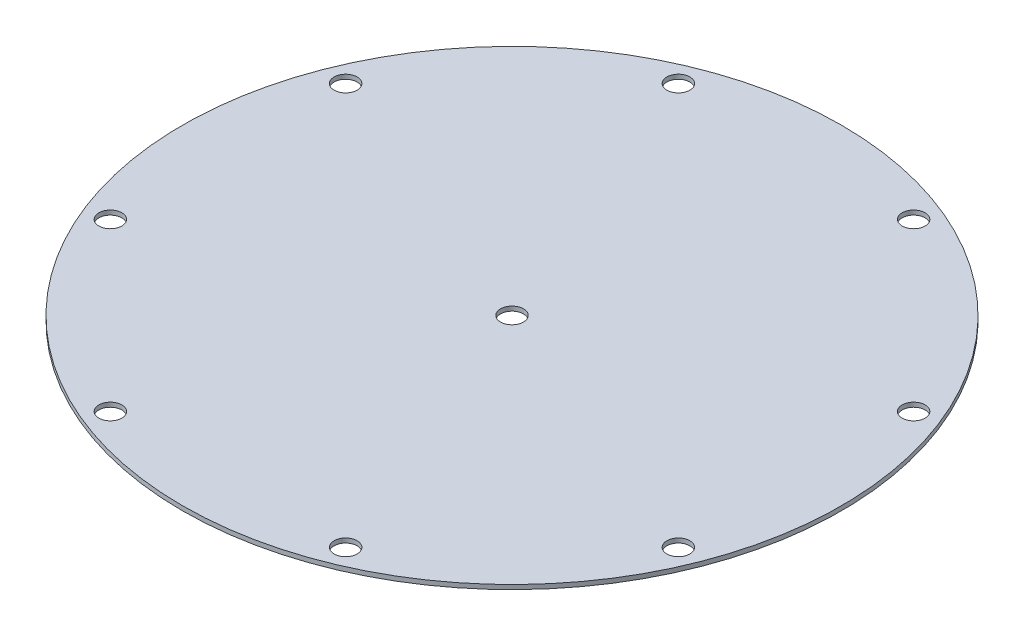
SolidWorks part; units mm, degrees
material "6061-T6 (SS)"
ref_plane "Front Plane" through (0, 0, 0) normal (0, 0, 1) x (1, 0, 0)
ref_plane "Top Plane" through (0, 0, 0) normal (0, 1, 0) x (1, 0, 0)
ref_plane "Right Plane" through (0, 0, 0) normal (1, 0, 0) x (0, 0, -1)
sketch "Sketch2" plane through (0, 0, 0) normal (1, 0, 0) x (0, 0, -1)
  line L0 (0, 0) -> (-74.375, 0)
  line L1 (-74.375, 0) -> (-74.375, 1)
  line L2 (-74.375, 1) -> (0, 1)
  line L5 (0, 1) -> (0, 0)
  dimension "D1" = 74.375
  dimension "D2" = 1
ref_axis "Axis1" through (0, -0.05, 0) along (0, 1, 0)
revolve "Revolve1" add sketch "Sketch2" angle 360 about axis through (0, -0.05, 0) along (0, 1, 0)
hole_wizard "#6 (0.204) Diameter Hole1" positions "Sketch6" profile "Sketch7" hole size "#6" standard "ANSI Inch" end condition through all
sketch "Sketch6" plane through (0, 1, 0) normal (0, 1, 0) x (1, 0, 0)
  line L0 (0, 0) -> (-53.438, 129.0108) construction
  line L2 (0, 0) -> (0, 109.0908) construction
  point P0 (-26.5487, 64.0941)
  dimension "D1" = 22.5
  dimension "D2" = 69.375
sketch "Sketch7" plane through (-26.5487, 1, -64.0941) normal (1, 0, 0) x (0, 0, 1)
  line L0 (0, 0) -> (0, 1)
  line L1 (0, 1) -> (2.5908, 1)
  line L2 (2.5908, 1) -> (2.5908, 0)
  line L5 (2.5908, 0) -> (0, 0)
  line L11 (0, -6.35) -> (0, 107.95) construction
  dimension "Thru Hole Dia." = 5.1816
  dimension "Thru Hole Depth" = 1
pattern_circular "CirPattern3" count 8 over 360 about axis through (0, -0.05, 0) along (0, 1, 0) of "#6 (0.204) Diameter Hole1"
hole_wizard "#6 (0.204) Diameter Hole2" positions "Sketch8" profile "Sketch9" hole size "#6" standard "ANSI Inch" end condition through all
sketch "Sketch8" plane through (0, 1, 0) normal (0, 1, 0) x (1, 0, 0)
  line L0 (0, 0) -> (106.3094, -1.7118) construction
  point P7 (0, 0)
sketch "Sketch9" plane through (0, 1, 0) normal (1, 0, 0) x (0, 0, 1)
  line L0 (0, 0) -> (0, 1)
  line L1 (0, 1) -> (2.5908, 1)
  line L2 (2.5908, 1) -> (2.5908, 0)
  line L5 (2.5908, 0) -> (0, 0)
  line L11 (0, -6.35) -> (0, 107.95) construction
  dimension "Thru Hole Dia." = 5.1816
  dimension "Thru Hole Depth" = 1
equation "\"TubeDiameter\" = 6.250in"
equation "\"D1@Sketch2\"=\"TubeDiameter\"/2-5mm"
equation "\"D2@Sketch6\"=\"TubeDiameter\"/2-10mm"
